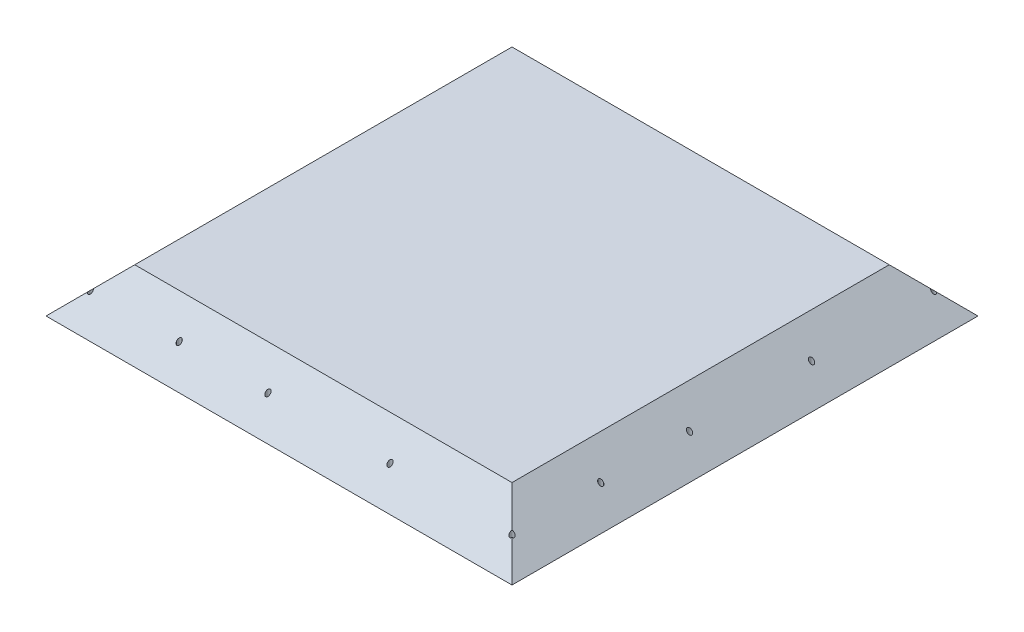
SolidWorks part; units mm, degrees
ref_plane "Front Plane" through (0, 0, 0) normal (0, 0, 1) x (1, 0, 0)
ref_plane "Top Plane" through (0, 0, 0) normal (0, 1, 0) x (1, 0, 0)
ref_plane "Right Plane" through (0, 0, 0) normal (1, 0, 0) x (0, 0, -1)
sketch "CenterSketch1" plane through (0, 0, 0) normal (0, 1, 0) x (1, 0, 0)
  line L1 (0, 0) -> (210, 0)
  line L2 (0, 0) -> (0, 210)
  line L3 (0, 210) -> (210, 210)
  line L4 (210, 0) -> (210, 210)
  dimension "D1" = 210
  dimension "D2" = 210
extrude "CenterBoss-Extrude1" add sketch "CenterSketch1" along normal blind 20
sketch "TabHolesSketch1" plane through (0, 20, 0) normal (0, 1, 0) x (1, 0, 0)
  line L4 (0, 0) -> (210, 0) construction
  line L5 (0, 210) -> (0, 0) construction
  line L6 (210, 0) -> (210, 210) construction
  line L7 (210, 210) -> (0, 210) construction
  circle A0 centre (10, 10) radius 1
  circle A1 centre (200, 10) radius 1
  circle A2 centre (200, 200) radius 1
  circle A3 centre (10, 200) radius 1
  circle A4 centre (65, 200) radius 1
  circle A5 centre (120, 200) radius 1
  circle A6 centre (160, 200) radius 1
  circle A7 centre (10, 160) radius 1
  circle A8 centre (10, 65) radius 1
  circle A9 centre (10, 120) radius 1
  circle A10 centre (50, 10) radius 1
  circle A11 centre (90, 10) radius 1
  circle A12 centre (145, 10) radius 1
  circle A13 centre (200, 145) radius 1
  circle A14 centre (200, 90) radius 1
  circle A15 centre (200, 50) radius 1
  dimension "D16" = 2
  dimension "D4" = 55
  dimension "D5" = 55
  dimension "D7" = 55
  dimension "D8" = 55
  dimension "D9" = 40
  dimension "D10" = 40
  dimension "D11" = 55
  dimension "D12" = 55
  dimension "D13" = 55
  dimension "D14" = 55
  dimension "D15" = 40
  dimension "D6" = 40
  dimension "D2" = 10
  dimension "D18" = 10
  dimension "D17" = 10
  dimension "D3" = 10
extrude "TabHolesCut-Extrude1" cut sketch "TabHolesSketch1" against normal blind 17
chamfer "Chamfer1" distance 20 distance2 20 4 edges at (105, 20, 0) (210, 20, -105) (0, 20, -105) (105, 20, -210)
equation "\"BedThickness\"= 20mm"
equation "\"BedOverlap\"= 20mm"
equation "\"BedThirdSize\"= 70mm"
equation "\"D1@CenterBoss-Extrude1\"=\"BedThickness\""
equation "\"BedInnerSquareWidth\"= \"BedThirdSize\" * 3'Equals 210"
equation "\"BedInnerSquareLength\"= \"BedInnerSquareWidth\""
equation "\"D1@CenterSketch1\"=\"BedInnerSquareLength\""
equation "\"D2@CenterSketch1\"=\"BedInnerSquareWidth\""
equation "\"D2@TabHolesSketch1\"=\"BedOverlap\"/2"
equation "\"D18@TabHolesSketch1\"=\"BedOverlap\"/2"
equation "\"D17@TabHolesSketch1\"=\"BedOverlap\"/2"
equation "\"D3@TabHolesSketch1\"=\"BedOverlap\"/2"
equation "\"D1@Chamfer1\"=\"BedThickness\""
equation "\"D3@Chamfer1\"=\"BedOverlap\""
equation "\"D1@TabHolesCut-Extrude1\" = \"BedThickness\" - \"StandardWallThickness\""
equation "\"StandardWallThickness\"= 3mm"
